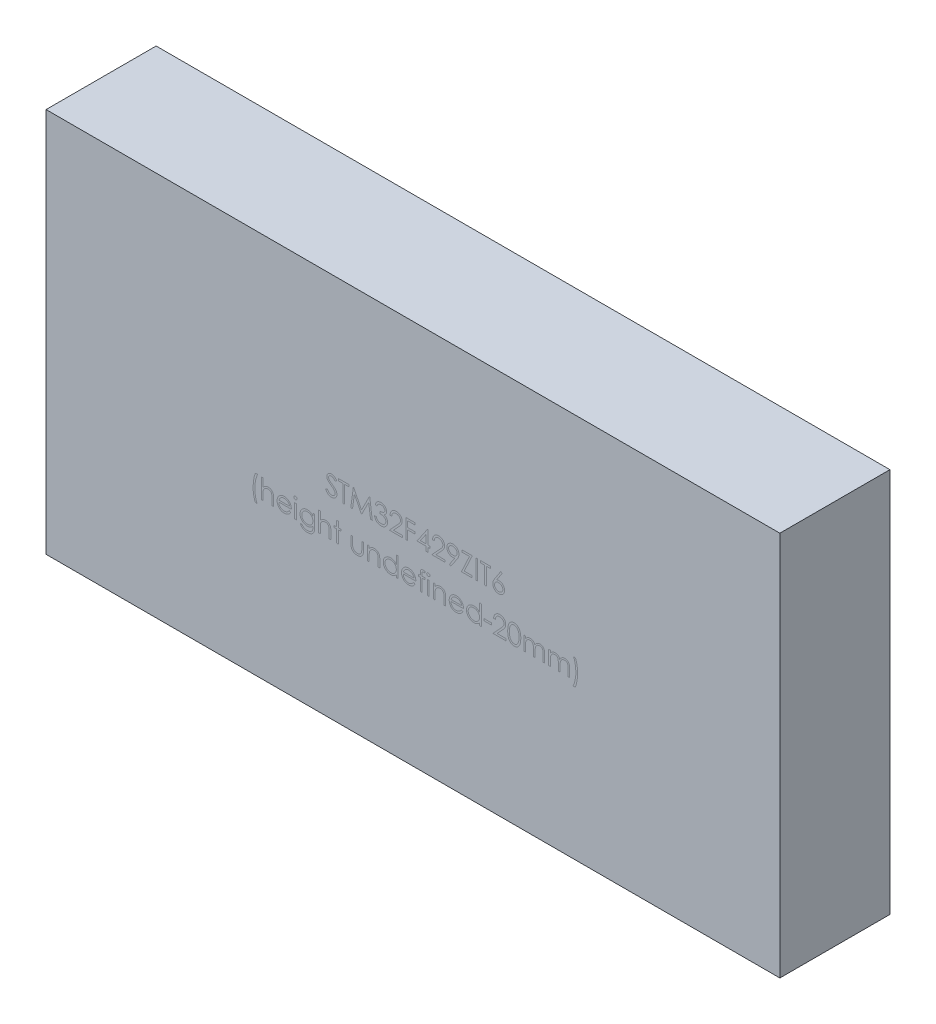
SolidWorks part; units mm, degrees
ref_plane "정면" through (0, 0, 0) normal (0, 0, 1) x (1, 0, 0)
ref_plane "윗면" through (0, 0, 0) normal (0, 1, 0) x (1, 0, 0)
ref_plane "우측면" through (0, 0, 0) normal (1, 0, 0) x (0, 0, -1)
sketch "스케치1" plane through (0, 0, 0) normal (0, 0, 1) x (1, 0, 0)
  line L1 (-66.67, 35) -> (66.67, 35)
  line L2 (-66.67, 35) -> (-66.67, -35)
  line L3 (-66.67, -35) -> (66.67, -35)
  line L4 (66.67, 35) -> (66.67, -35)
  line L5 (-66.67, 35) -> (66.67, -35) construction
  line L6 (-66.67, -35) -> (66.67, 35) construction
  point P0 (0, 0)
  dimension "D1" = 133.34
  dimension "D2" = 70
extrude "보스-돌출1" add sketch "스케치1" along normal blind 20
ref_plane "평면1" through (0, 0, 30) normal (0, 0, 1) x (1, 0, 0)
sketch "스케치3" plane through (0, 0, 30) normal (0, 0, 1) x (1, 0, 0)
  line L0 (-66.67, 0) -> (67.5821, 0) construction
  line L1 (-66.67, 35) -> (-66.67, -35) construction
  text T0 "STM32F429ZIT6\r\n(height undefined-20mm)"
wrap "곡면 포장1" sketch "스케치3" wrap type scribe source sketch "스케치3" face at (0, 0, 20)
